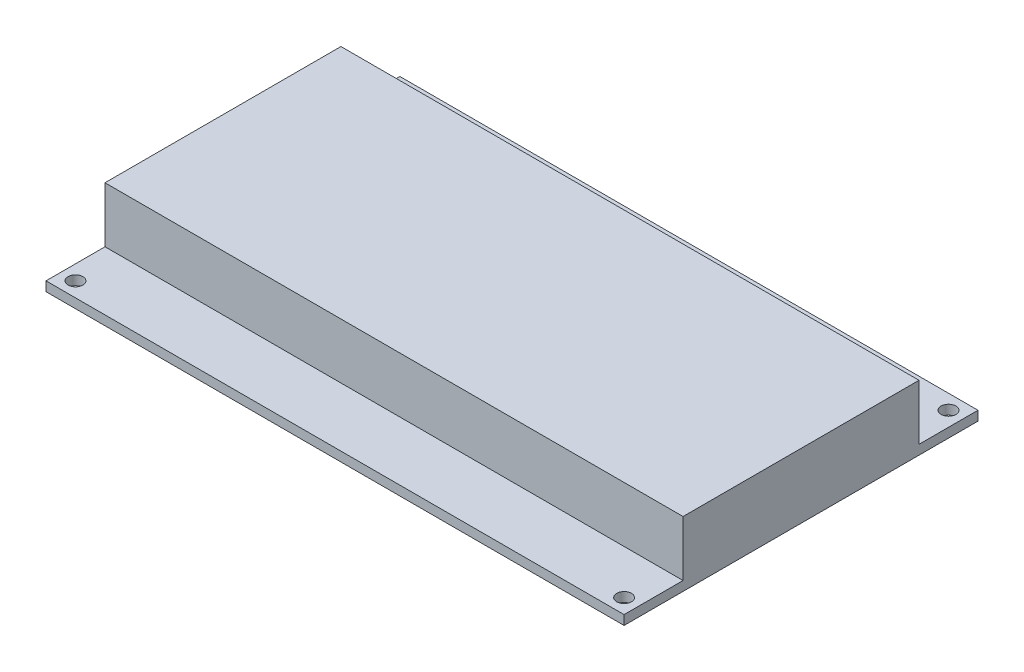
SolidWorks part; units mm, degrees
ref_plane "Спереди" through (0, 0, 0) normal (0, 0, 1) x (1, 0, 0)
ref_plane "Сверху" through (0, 0, 0) normal (0, 1, 0) x (1, 0, 0)
ref_plane "Справа" through (0, 0, 0) normal (1, 0, 0) x (0, 0, -1)
sketch "Эскиз1" plane through (0, 0, 0) normal (0, 1, 0) x (1, 0, 0)
  line L1 (49, 30) -> (-49, 30)
  line L2 (49, 30) -> (49, -30)
  line L3 (49, -30) -> (-49, -30)
  line L4 (-49, 30) -> (-49, -30)
  line L5 (49, 30) -> (-49, -30) construction
  line L6 (49, -30) -> (-49, 30) construction
  line L7 (49, 20) -> (-49, 20)
  line L8 (49, 20) -> (49, -20)
  line L9 (49, -20) -> (-49, -20)
  line L10 (-49, 20) -> (-49, -20)
  line L11 (49, 20) -> (-49, -20) construction
  line L12 (49, -20) -> (-49, 20) construction
  point P0 (0, 0)
  point P6 (0, 0)
  dimension "D1" = 98
  dimension "D2" = 60
  dimension "D3" = 40
extrude "Бобышка-Вытянуть1" add sketch "Эскиз1" along normal blind 1.6 contours L7 L2 L1 L4 | L9 L2 L7 L4 | L2 L9 L4 L3 region at (0, 0, -25) region at (0, 0, 0) region at (0, 0, 25)
extrude "Бобышка-Вытянуть2" add sketch "Эскиз1<4>" along normal blind 11 contours L9 L2 L7 L4 region at (0, 0, 0)
sketch "Эскиз1<4>" plane through (0, 0, 0) normal (0, 1, 0) x (1, 0, 0) same geometry as "Эскиз1"
sketch "Эскиз2" plane through (0, 0, 0) normal (0, -1, 0) x (1, 0, 0)
  line L1 (-39, -30) -> (6, -30)
  line L2 (-39, -30) -> (-39, -5)
  line L3 (-39, -5) -> (6, -5)
  line L4 (6, -30) -> (6, -5)
  line L6 (-49, -30) -> (-49, 30) construction
  line L7 (49, -30) -> (-49, -30) construction
  dimension "D1" = 45
  dimension "D2" = 25
  dimension "D3" = 10
extrude "Бобышка-Вытянуть3" add sketch "Эскиз2" along normal blind 13
sketch "Эскиз3" plane through (0, 0, 0) normal (0, -1, 0) x (1, 0, 0)
  line L0 (49, 30) -> (-49, -30) construction
  line L1 (0, -27.5) -> (0, 27.5) construction
  line L2 (-46.5, 27.5) -> (46.5, 27.5) construction
  line L3 (46.5, 0) -> (-46.5, 0) construction
  line L4 (-46.5, -27.5) -> (46.5, -27.5) construction
  line L5 (-46.5, -27.5) -> (-46.5, 27.5) construction
  line L6 (-46.5, 27.5) -> (46.5, 27.5) construction
  line L7 (46.5, -27.5) -> (46.5, 27.5) construction
  line L8 (-46.5, -27.5) -> (46.5, 27.5) construction
  line L9 (-46.5, 27.5) -> (46.5, -27.5) construction
  circle A0 centre (46.5, 27.5) radius 1.25
  circle A1 centre (-46.5, 27.5) radius 1.25
  circle A2 centre (-46.5, -27.5) radius 1.25
  circle A3 centre (46.5, -27.5) radius 1.25
  point P4 (0, 0)
  point P8 (0, 0)
  point P12 (0, 27.5)
  dimension "D3" = 2.5
  dimension "D1" = 93
  dimension "D2" = 55
extrude "Вырез-Вытянуть1" cut sketch "Эскиз3" against normal up to next
